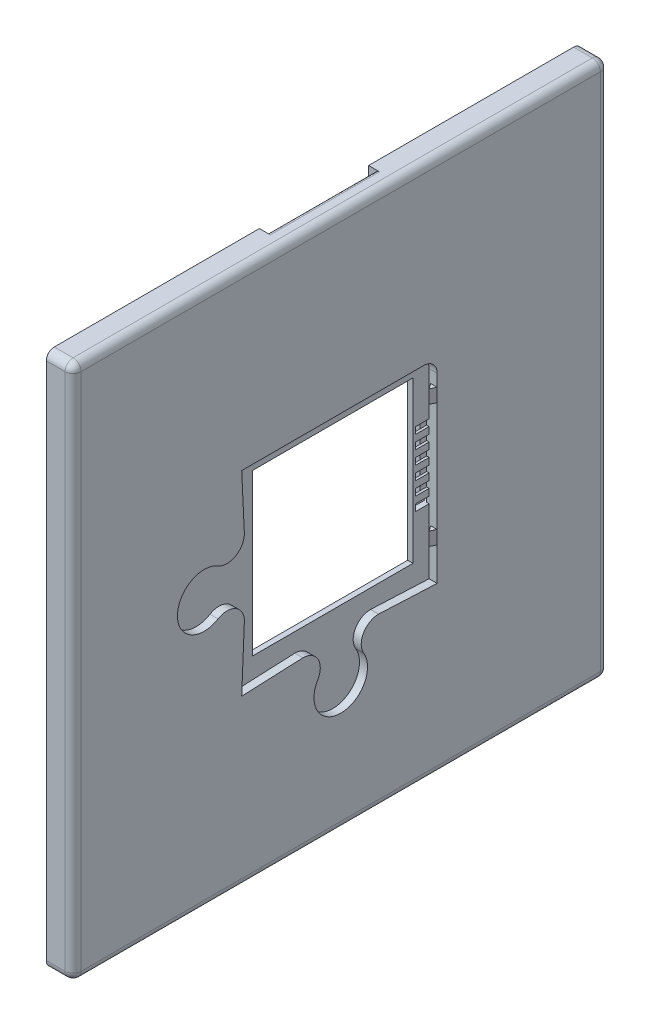
SolidWorks part; units mm, degrees
ref_plane "Front Plane" through (0, 0, 0) normal (0, 0, 1) x (1, 0, 0)
ref_plane "Top Plane" through (0, 0, 0) normal (0, 1, 0) x (1, 0, 0)
ref_plane "Right Plane" through (0, 0, 0) normal (1, 0, 0) x (0, 0, -1)
sketch "Sketch1" plane through (0, 0, 0) normal (1, 0, 0) x (0, 0, -1)
  line L1 (-100, 100) -> (100, 100)
  line L2 (-100, 100) -> (-100, -100)
  line L3 (-100, -100) -> (100, -100)
  line L4 (100, 100) -> (100, -100)
  point P6 (-100, 0)
  dimension "D1" = 200
  dimension "D2" = 200
  dimension "D3" = 100
extrude "Boss-Extrude1" add sketch "Sketch1" along normal blind 10
sketch "Sketch2" plane through (0, 0, 0) normal (-1, 0, 0) x (0, 0, 1)
  line L0 (-35.5, 35.5) -> (-25.5, 35.5)
  line L1 (-35.5, 35.5) -> (-25.5, 35.5)
  line L2 (-35.5, 35.5) -> (-35.5, -35.5)
  line L3 (-35.5, -35.5) -> (35.5, -35.5)
  line L4 (35.5, 35.5) -> (35.5, -35.5)
  line L5 (-25.5, 35.5) -> (-5, 44.5)
  line L6 (-5, 44.5) -> (5, 44.5)
  line L7 (5, 44.5) -> (25.5, 35.5)
  line L8 (25.5, 35.5) -> (35.5, 35.5)
  line L9 (25.5, 35.5) -> (35.5, 35.5)
  line L10 (36.5, 35.5) -> (36.5, -36.5)
  line L11 (-36.5, -36.5) -> (36.5, -36.5)
  line L12 (-36.5, 35.5) -> (-36.5, -36.5)
  line L13 (-35.5, 36.5) -> (-25.5, 36.5)
  line L14 (-25.902, 36.4156) -> (-5.2098, 45.5)
  line L15 (-5.2098, 45.5) -> (5.2098, 45.5)
  line L16 (5.2098, 45.5) -> (25.902, 36.4156)
  line L17 (25.5, 36.5) -> (35.5, 36.5)
  line L18 (-36.5, 35.5) -> (-36.5, 36.5)
  line L19 (-36.5, 36.5) -> (-35.5, 36.5)
  line L20 (35.5, 36.5) -> (36.5, 36.5)
  line L21 (36.5, 36.5) -> (36.5, 35.5)
  point P5 (0, -35.5)
  point P12 (35.5, 0)
  dimension "D1" = 10
  dimension "D2" = 71
  dimension "D3" = 71
  dimension "D4" = 10
  dimension "D5" = 10
  dimension "D6" = 80
  dimension "D7" = 20.5
  dimension "D8" = 1
extrude "Cut-Extrude1" cut sketch "Sketch2" against normal blind 5 contours L21 L20 L17 L16 L15 L14 L13 L19 L18 L12 L11 L10 L7 L8 L4 L3 L2 L0 L5 L6 | L8 L7 L6 L5 L0 L2 L3 L4 region at (0, 2.0136, 0) region at (0, -0.5, 36.3902)
sketch "Sketch3" plane through (5, 0, 0) normal (-1, 0, 0) x (0, 0, 1)
  line L1 (-30, 30) -> (30, 30)
  line L2 (-30, 30) -> (-30, -30)
  line L3 (-30, -30) -> (30, -30)
  line L4 (30, 30) -> (30, -30)
  point P4 (0, -30)
  point P6 (30, 0)
  dimension "D1" = 60
  dimension "D2" = 60
extrude "Cut-Extrude2" cut sketch "Sketch3" against normal through all
sketch "Sketch4" plane through (10, 0, 0) normal (1, 0, 0) x (0, 0, -1)
  line L2 (-36, 35) -> (-36, 14.1421) construction
  line L3 (-36, -37) -> (-14.1421, -37) construction
  line L8 (36, 30) -> (36, -37)
  line L9 (37, -38) -> (-37, -38) construction
  line L10 (-37, 37) -> (37, 37) construction
  line L11 (-37, 37) -> (-37, -38) construction
  line L13 (37, 37) -> (37, -38) construction
  line L14 (14.1421, -37) -> (36, -37) construction
  line L15 (31, 35) -> (-36, 35)
  line L16 (-36, -14.1421) -> (-36, -37) construction
  line L17 (-36, 14.1421) -> (-37, 35)
  line L18 (-37, 35) -> (-36, 35)
  line L19 (-14.1421, -37) -> (-37, -38)
  line L20 (-37, -38) -> (-36, -14.1421)
  line L21 (14.1421, -37) -> (36, -38)
  line L22 (36, -38) -> (36, -37)
  arc A6 (-8.571, -46.8485) -> (8.571, -46.8485) centre (0, -52) ccw
  arc A7 (14.1421, -37) -> (8.571, -46.8485) centre (14.1421, -43.5) ccw
  arc A8 (-8.571, -46.8485) -> (-14.1421, -37) centre (-14.1421, -43.5) ccw
  arc A9 (-45.8485, 8.571) -> (-36, 14.1421) centre (-42.5, 14.1421) ccw
  arc A10 (-36, -14.1421) -> (-45.8485, -8.571) centre (-42.5, -14.1421) ccw
  arc A11 (-45.8485, 8.571) -> (-45.8485, -8.571) centre (-51, 0) ccw
  arc A12 (31, 35) -> (36, 30) centre (31, 30) cw
  point P9 (36, 35)
  point P22 (0.5, -0.5)
  point P24 (0, 0)
  dimension "D3" = 2
  dimension "D4" = 2
  dimension "D6" = 15
  dimension "D8" = 1
  dimension "D9" = 1
  dimension "D12" = 20
  dimension "D13" = 13
  dimension "D14" = 13
  dimension "D7" = 20.8579
  dimension "D5" = 5
  dimension "D1" = 72
  dimension "D2" = 72
  dimension "D10" = 1
  dimension "D11" = 15
  dimension "D15" = 36
extrude "Cut-Extrude3" cut sketch "Sketch4" against normal blind 3
sketch "Sketch8" plane through (0, 0, 0) normal (-1, 0, 0) x (0, 0, 1)
  line L1 (20.4, 100) -> (-20.4, 100)
  line L2 (20.4, 100) -> (20.4, 90.8)
  line L3 (20.4, 90.8) -> (-20.4, 90.8)
  line L4 (-20.4, 100) -> (-20.4, 90.8)
  line L5 (-100, -100) -> (-100, 100) construction
  line L6 (-100, 100) -> (100, 100) construction
  dimension "D2" = 79.6
  dimension "D3" = 40.8
  dimension "D4" = 9.2
extrude "Cut-Extrude4" cut sketch "Sketch8" against normal blind 2.6
shell "Shell1" [suppressed] thickness 5
sketch "Sketch9" plane through (0, 0, 0) normal (-1, 0, 0) x (0, 0, 1)
  line L0 (-95, 95) -> (-95, -95)
  line L1 (-95, -95) -> (95, -95)
  line L2 (95, -95) -> (95, 95)
  line L3 (95, 95) -> (25.4, 95)
  line L4 (25.4, 95) -> (25.4, 85.8)
  line L5 (25.4, 85.8) -> (-25.4, 85.8)
  line L6 (-25.4, 85.8) -> (-25.4, 95)
  line L7 (-25.4, 95) -> (-95, 95)
  line L8 (-41.5, 41.5) -> (-41.5, -41.5)
  line L9 (-41.5, -41.5) -> (41.5, -41.5)
  line L10 (41.5, -41.5) -> (41.5, 41.5)
  line L14 (-100, -100) -> (-100, 100) construction
  line L15 (-100, 100) -> (-20.4, 100) construction
  line L16 (-20.4, 100) -> (-20.4, 90.8) construction
  line L17 (20.4, 90.8) -> (20.4, 100) construction
  line L18 (-20.4, 90.8) -> (20.4, 90.8) construction
  line L19 (100, 100) -> (100, -100) construction
  line L20 (100, -100) -> (-100, -100) construction
  line L21 (-36.5, -36.5) -> (-36.5, 36.5) construction
  line L22 (-36.5, -36.5) -> (36.5, -36.5) construction
  line L23 (36.5, 36.5) -> (36.5, -36.5) construction
  line L24 (-5.2098, 45.5) -> (5.2098, 45.5)
  line L27 (-41.5, 41.5) -> (-19.2962, 41.5)
  line L28 (-19.2962, 41.5) -> (-5.6295, 47.5)
  line L29 (-5.6295, 47.5) -> (5.6295, 47.5) construction
  line L30 (5.6295, 47.5) -> (19.2962, 41.5)
  line L32 (19.2962, 41.5) -> (41.5, 41.5)
  line L33 (-36.5, 36.5) -> (-25.7098, 36.5) construction
  line L35 (-25.7098, 36.5) -> (-5.2098, 45.5) construction
  line L36 (5.2098, 45.5) -> (25.7098, 36.5) construction
  line L37 (-5.2098, 45.5) -> (5.2098, 45.5) construction
  line L38 (5.2098, 45.5) -> (25.7098, 36.5) construction
  line L39 (25.7098, 36.5) -> (36.5, 36.5) construction
  line L40 (-25.7098, 36.5) -> (-5.2098, 45.5) construction
  line L41 (-12.5, -41.5) -> (-12.5, -64.5)
  line L42 (-12.5, -64.5) -> (12.5, -64.5)
  line L43 (12.5, -64.5) -> (12.5, -41.5)
  line L44 (41.5, 12.5) -> (64.5, 12.5)
  line L45 (64.5, 12.5) -> (64.5, -12.5)
  line L46 (64.5, -12.5) -> (41.5, -12.5)
  line L47 (-5.2098, 45.5) -> (-5.6295, 47.5)
  line L48 (5.2098, 45.5) -> (5.6295, 47.5)
  point P59 (64.5, 0)
  point P62 (41.5, 0)
  point P63 (0, -64.5)
  point P64 (0, -41.5)
  line M34 (-5.2098, 45.5) -> (5.2098, 45.5)
  dimension "D1" = 5
  dimension "D2" = 5
  dimension "D3" = 5
  dimension "D4" = 5
  dimension "D5" = 5
  dimension "D6" = 5
  dimension "D7" = 5
  dimension "D8" = 5
  dimension "D9" = 5
  dimension "D10" = 5
  dimension "D11" = 5
  dimension "D12" = 5
  dimension "D13" = 2
  dimension "D14" = 2
  dimension "D15" = 5
  dimension "D16" = 2
  dimension "D17" = 25
  dimension "D18" = 25
  dimension "D19" = 23
  dimension "D20" = 23
extrude "Cut-Extrude5" cut sketch "Sketch9" against normal blind 7 contours L6 L7 L0 L1 L2 L3 L4 L5 L45 L46 L10 L9 L43 L42 L41 L8 L27 L28 L29 L30 L32 L44 | L29 L47 L48 M34 region at (0, 92.313, -60.2) region at (0, 46.5129, 0)
fillet "Fillet1" radius 3 3 edges at (5, 100, 100) (10, 100, 0) (10, 0, 100)
sketch "Sketch10" plane through (0, -64.5, 0) normal (0, -1, 0) x (1, 0, 0)
  line L0 (7, -12.5) -> (7, 12.5) construction
  line L1 (2.9, -2.6) -> (6, -2.6)
  line L2 (2.9, -2.6) -> (2.9, 2.6)
  line L3 (2.9, 2.6) -> (6, 2.6)
  line L4 (6, -2.6) -> (6, 2.6)
  line L6 (7, -12.5) -> (0, -12.5) construction
  point P8 (2.9, 0)
  dimension "D1" = 5.2
  dimension "D2" = 3.1
  dimension "D3" = 1
  dimension "D4" = 12.5
extrude "Cut-Extrude6" cut sketch "Sketch10" against normal blind 12.5
fillet "Fillet2" radius 1 4 edges at (4.45, -64.5, -2.6) (6, -64.5, 0) (4.45, -64.5, 2.6) (2.9, -64.5, 0)
sketch "Sketch11" plane through (0, 0, 64.5) normal (0, 0, 1) x (1, 0, 0)
  line L1 (2.9, 2.6) -> (6, 2.6)
  line L2 (2.9, 2.6) -> (2.9, -2.6)
  line L3 (2.9, -2.6) -> (6, -2.6)
  line L4 (6, 2.6) -> (6, -2.6)
  line L5 (7, -12.5) -> (0, -12.5) construction
  line L6 (7, 12.5) -> (7, -12.5) construction
  point P4 (2.9, 0)
  dimension "D1" = 3.1
  dimension "D2" = 5.2
  dimension "D3" = 12.5
  dimension "D4" = 1
extrude "Cut-Extrude7" cut sketch "Sketch11" against normal blind 13.5
fillet "Fillet3" radius 1 4 edges at (2.9, 0, 64.5) (4.45, -2.6, 64.5) (6, 0, 64.5) (4.45, 2.6, 64.5)
fillet "Fillet4" radius 4 4 edges at (3.5, 12.5, 64.5) (3.5, -12.5, 64.5) (3.5, -64.5, 12.5) (3.5, -64.5, -12.5)
sketch "Sketch12" plane through (0, 0, 0) normal (-1, 0, 0) x (0, 0, 1)
  line L0 (-95, 95) -> (-95, -95) construction
  line L1 (-95, -84.8) -> (-99, -84.8)
  line L2 (-95, -84.8) -> (-95, -90)
  line L3 (-95, -90) -> (-99, -90)
  line L4 (-99, -84.8) -> (-99, -90)
  line L5 (-100, -100) -> (-100, 100) construction
  line L6 (100, -100) -> (-100, -100) construction
  dimension "D1" = 1
  dimension "D2" = 10
  dimension "D3" = 5.2
extrude "Cut-Extrude8" cut sketch "Sketch12" against normal blind 2
sketch "Sketch13" plane through (2, 0, 0) normal (-1, 0, 0) x (0, 0, 1)
  line L0 (-99, -90) -> (-95, -90) construction
  line L1 (-99, -84.8) -> (-96, -84.8)
  line L2 (-99, -84.8) -> (-99, -90)
  line L3 (-99, -90) -> (-96, -90)
  line L4 (-96, -84.8) -> (-96, -90)
  dimension "D1" = 3
extrude "Cut-Extrude9" cut sketch "Sketch13" against normal blind 6
sketch "Sketch14" plane through (7, 0, 0) normal (-1, 0, 0) x (0, 0, 1)
  line L0 (95, -95) -> (95, 95) construction
  line L1 (95, -82.4) -> (92, -82.4)
  line L2 (95, -82.4) -> (95, -92.4)
  line L3 (95, -92.4) -> (92, -92.4)
  line L4 (92, -82.4) -> (92, -92.4)
  line L5 (-99, -84.8) -> (-99, -90) construction
  point P8 (-99, -87.4)
  point P9 (92, -87.4)
  dimension "D1" = 10
  dimension "D2" = 3
extrude "Boss-Extrude2" add sketch "Sketch14" along normal blind 7
sketch "Sketch16" plane through (0, 0, 92) normal (0, 0, -1) x (-1, 0, 0)
  line L0 (0, -82.4) -> (0, -92.4) construction
  line L1 (-4.2, -84.9) -> (-1, -84.9)
  line L2 (-4.2, -84.9) -> (-4.2, -89.9)
  line L3 (-4.2, -89.9) -> (-1, -89.9)
  line L4 (-1, -84.9) -> (-1, -89.9)
  point P6 (0, -87.4)
  point P7 (-1, -87.4)
  dimension "D1" = 3.2
  dimension "D2" = 1
  dimension "D3" = 5
extrude "Cut-Extrude10" cut sketch "Sketch16" against normal blind 6
fillet "Fillet5" radius 1 3 edges at (2.6, -89.9, 92) (4.2, -87.4, 92) (2.6, -84.9, 92)
sketch "Sketch17" plane through (0, 0, 0) normal (-1, 0, 0) x (0, 0, 1)
  line L1 (-65.5796, 65.977) -> (65.5796, 65.977)
  line L2 (-65.5796, 65.977) -> (-65.5796, -65.977)
  line L3 (-65.5796, -65.977) -> (65.5796, -65.977)
  line L4 (65.5796, 65.977) -> (65.5796, -65.977)
  point P4 (0, 65.977)
  point P6 (-65.5796, 0)
  dimension "D1" = 131.954
  dimension "D2" = 131.1591
extrude "Cut-Extrude11" cut sketch "Sketch17" against normal blind 2.1
sketch "Sketch18" plane through (0, 0, 0) normal (-1, 0, 0) x (0, 0, 1)
  line L0 (100, -100) -> (-100, -100) construction
  line L1 (-100, -100) -> (-100, 100) construction
  line L2 (20.4, 100) -> (-20.4, 100) construction
  line L3 (-20.4, 100) -> (-20.4, 90.8) construction
  line L4 (-20.4, 90.8) -> (20.4, 90.8) construction
  line L5 (20.4, 90.8) -> (20.4, 100) construction
  line L6 (20.4, 100) -> (97, 100) construction
  line L7 (100, 97) -> (100, -100) construction
  line L8 (100, -100) -> (-100, -100) construction
  line L9 (-100, -100) -> (-100, 100) construction
  line L10 (-100, 100) -> (-20.4, 100) construction
  line L11 (-20.4, 100) -> (-20.4, 90.8) construction
  line L12 (-20.4, 90.8) -> (20.4, 90.8) construction
  line L13 (20.4, 90.8) -> (20.4, 100) construction
  line L14 (20.4, 100) -> (97, 100) construction
  line L15 (100, 97) -> (100, -100) construction
  line L16 (-97, 97) -> (-23.4, 97)
  line L17 (-23.4, 97) -> (-23.4, 88.4)
  line L18 (-23.4, 88.4) -> (23.4, 88.4)
  line L19 (23.4, 88.4) -> (23.4, 97)
  line L20 (23.4, 97) -> (97, 97)
  line L21 (97, 97) -> (97, -97)
  line L22 (97, -97) -> (-97, -97)
  line L23 (-97, -97) -> (-97, 97)
  line L24 (92, -92.4) -> (97, -92.4)
  line L25 (97, -92.4) -> (97, -82.4)
  line L26 (97, -82.4) -> (92, -82.4)
  line L27 (92, -82.4) -> (92, -92.4)
  line L28 (95, -82.4) -> (92, -82.4) construction
  arc A1 (100, 97) -> (97, 100) centre (97, 97) ccw construction
  arc A3 (100, 97) -> (97, 100) centre (97, 97) ccw construction
  point P19 (23.4, 92.7)
  line M19 (-95, -95) -> (-95, -90)
  line M20 (-95, -90) -> (-99, -90)
  line M22 (-99, -84.8) -> (-95, -84.8)
  line M23 (-95, -84.8) -> (-95, 95)
  line M24 (-95, 95) -> (-25.4, 95)
  line M25 (-25.4, 95) -> (-25.4, 85.8)
  line M26 (-25.4, 85.8) -> (25.4, 85.8)
  line M27 (25.4, 85.8) -> (25.4, 95)
  line M28 (25.4, 95) -> (95, 95)
  line M29 (95, 95) -> (95, -82.4)
  line M30 (95, -82.4) -> (92, -82.4)
  line M31 (92, -82.4) -> (92, -92.4)
  line M32 (92, -92.4) -> (95, -92.4)
  line M33 (95, -92.4) -> (95, -95)
  line M34 (95, -95) -> (-95, -95)
  dimension "D2" = 3
  dimension "D1" = 3
  dimension "D3" = 6
  dimension "D4" = 8.6
  dimension "D5" = 3
  dimension "D6" = 3
  dimension "D7" = 46.8
  dimension "D8" = 11.6
  dimension "D9" = 76.6
extrude "Cut-Extrude12" cut sketch "Sketch18" against normal blind 2 contours L26 L21 L20 L19 L18 L17 L16 L23 M22 M23 M24 M25 M26 M27 M28 M29 | L23 M20 M19 M34 M33 M32 M31 M30 M29 M28 M27 M26 M25 M24 M23 M22 | L24 L23 L22 L21 M33 M34 M19 M20 region at (0, 96.7341, -60.2) region at (0, -1.1382, -0.1068) region at (0, -95.8835, -1.1429)
sketch "Sketch19" plane through (7, 0, 0) normal (1, 0, 0) x (0, 0, -1)
  line L0 (36, -38) -> (36, 30) construction
  line L1 (36, 13.75) -> (31, 13.75)
  line L2 (36, 13.75) -> (36, -13.75)
  line L3 (36, -13.75) -> (31, -13.75)
  line L4 (31, 13.75) -> (31, -13.75)
  line L6 (36, 13.75) -> (31, 13.75)
  line L7 (36, 13.75) -> (36, 11.25)
  line L8 (36, 11.25) -> (31, 11.25)
  line L9 (31, 13.75) -> (31, 11.25)
  line L10 (36, 8.75) -> (31, 8.75)
  line L11 (36, 8.75) -> (36, 6.25)
  line L12 (36, 6.25) -> (31, 6.25)
  line L13 (31, 8.75) -> (31, 6.25)
  line L14 (36, 3.75) -> (31, 3.75)
  line L15 (36, 3.75) -> (36, 1.25)
  line L16 (36, 1.25) -> (31, 1.25)
  line L17 (31, 3.75) -> (31, 1.25)
  line L18 (36, -1.25) -> (31, -1.25)
  line L19 (36, -1.25) -> (36, -3.75)
  line L20 (36, -3.75) -> (31, -3.75)
  line L21 (31, -1.25) -> (31, -3.75)
  line L22 (36, -6.25) -> (31, -6.25)
  line L23 (36, -6.25) -> (36, -8.75)
  line L24 (36, -8.75) -> (31, -8.75)
  line L25 (31, -6.25) -> (31, -8.75)
  line L26 (36, -11.25) -> (31, -11.25)
  line L27 (36, -11.25) -> (36, -13.75)
  line L28 (36, -13.75) -> (31, -13.75)
  line L29 (31, -11.25) -> (31, -13.75)
  line L30 (30, -30) -> (30, 30) construction
  point P25 (31, 0)
  line M32 (36, -38) -> (36, 30)
  dimension "D2" = 2.5
  dimension "D3" = 2.5
  dimension "D4" = 2.5
  dimension "D5" = 2.5
  dimension "D6" = 2.5
  dimension "D7" = 2.5
  dimension "D8" = 2.5
  dimension "D9" = 2.5
  dimension "D10" = 2.5
  dimension "D11" = 2.5
  dimension "D12" = 2.5
  dimension "D13" = 1
extrude "Cut-Extrude13" cut sketch "Sketch19" against normal through all contours L26 L4 L3 M32 | L24 L2 L22 L4 | L20 L2 L18 L4 | L16 L2 L14 L4 | L12 L2 L10 L4 | L8 L2 L1 L4 region at (7, 12.5, -33.5) region at (7, 7.5, -33.5) region at (7, 2.5, -33.5) region at (7, -2.5, -33.5) region at (7, -7.5, -33.5) region at (7, -12.5, -33.5)
sketch "Sketch20" plane through (2.1, 0, 0) normal (-1, 0, 0) x (0, 0, 1)
  line L0 (-41.5, 41.5) -> (-41.5, -41.5) construction
  line L1 (-31, 13.75) -> (-41.5, 13.75)
  line L2 (-31, 13.75) -> (-31, -13.75)
  line L3 (-31, -13.75) -> (-41.5, -13.75)
  line L4 (-41.5, 13.75) -> (-41.5, -13.75)
  line L5 (-31, -13.75) -> (-36, -13.75) construction
  line L6 (-31, -13.75) -> (-31, -11.25) construction
extrude "Cut-Extrude14" cut sketch "Sketch20" against normal blind 4
chamfer "Chamfer1" distance 0.9 angle 45 1 edges at (5, 0, -31)
sketch "Sketch33" plane through (2.1, 0, 0) normal (-1, 0, 0) x (0, 0, 1)
  line L0 (-41.5, 13.75) -> (-41.5, 41.5) construction
  line L1 (-41.5, 18.75) -> (-36.5, 18.75)
  line L2 (-41.5, 18.75) -> (-41.5, -18.75)
  line L3 (-41.5, -18.75) -> (-36.5, -18.75)
  line L4 (-36.5, 18.75) -> (-36.5, -18.75)
  line L5 (-36.5, -13.75) -> (-36.5, -36.5) construction
  line L6 (-36.5, 13.75) -> (-41.5, 13.75) construction
  line L7 (-41.5, -13.75) -> (-36, -13.75) construction
  dimension "D1" = 5
  dimension "D2" = 5
extrude "Boss-Extrude10" add sketch "Sketch33" along normal blind 1 and the other way blind 1
sketch "Sketch34" plane through (0, 0, -41.5) normal (0, 0, -1) x (-1, 0, 0)
  line L0 (-3.1, 13.75) -> (-3.1, 17) construction
  line L1 (-6.1, 17) -> (-3.1, 17)
  line L2 (-6.1, 17) -> (-6.1, -17)
  line L3 (-6.1, -17) -> (-3.1, -17)
  line L4 (-3.1, 17) -> (-3.1, -17)
  line L5 (-6.1, 13.75) -> (-3.1, 13.75) construction
  line L6 (-6.1, -13.75) -> (-3.1, -13.75) construction
  line L7 (-3.1, -13.75) -> (-3.1, -17) construction
  line L8 (-7, 13.75) -> (-7, 30) construction
  dimension "D1" = 3
  dimension "D2" = 34
  dimension "D3" = 0.9
extrude "Cut-Extrude19" cut sketch "Sketch34" against normal blind 3
chamfer "Chamfer2" distance 1 angle 45 4 edges at (4.6, -17, -41.5) (3.1, 0, -41.5) (4.6, 17, -41.5) (6.1, 0, -41.5)
sketch "Sketch24" plane through (7, 0, 0) normal (-1, 0, 0) x (0, 0, 1)
  line L0 (-95, 95) -> (95, -95) construction
  line L1 (-95, -95) -> (95, 95) construction
  circle A0 centre (80, -80) radius 5
  circle A1 centre (80, -80) radius 0.75
  circle A2 centre (-80, -80) radius 0.75
  circle A3 centre (-80, -80) radius 5
  dimension "D1" = 10
  dimension "D2" = 1.5
  dimension "D4" = 1.5
  dimension "D5" = 10
  dimension "D3" = 15
  dimension "D6" = 15
extrude "Boss-Extrude5" add sketch "Sketch24" along normal blind 5
mirror "Mirror1" about plane through (0, 0, 0) normal (0, 1, 0) of "Boss-Extrude5"
sketch "Sketch25" plane through (2.1, 0, 0) normal (-1, 0, 0) x (0, 0, 1)
  line L0 (36.5, 36.5) -> (41.5, 41.5) construction
  line L1 (41.5, -41.5) -> (36.5, -36.5) construction
  line L2 (-41.5, -41.5) -> (-36.5, -36.5) construction
  line L3 (-41.5, 41.5) -> (-36.5, 36.5) construction
  line L5 (12.5, -41.5) -> (41.5, -41.5) construction
  line L6 (19.2962, 41.5) -> (41.5, 41.5) construction
  line L7 (-19.2962, 41.5) -> (-41.5, 41.5) construction
  circle A0 centre (-38.5, 38.5) radius 0.75
  circle A1 centre (38.5, 38.5) radius 0.75
  circle A2 centre (38.5, -38.5) radius 0.75
  circle A3 centre (-38.5, -38.5) radius 0.75
  dimension "D1" = 1.5
  dimension "D2" = 1.5
  dimension "D3" = 1.5
  dimension "D4" = 1.5
  dimension "D5" = 3
  dimension "D6" = 3
  dimension "D7" = 3
  dimension "D8" = 3
extrude "Cut-Extrude16" cut sketch "Sketch25" against normal blind 3.5
sketch "Sketch27" plane through (0, 95, 0) normal (0, -1, 0) x (1, 0, 0)
  line L0 (7, -25.4) -> (7, -95) construction
  line L1 (7, -41.5) -> (2, -41.5)
  line L2 (7, -41.5) -> (7, -65.5)
  line L3 (7, -65.5) -> (2, -65.5)
  line L4 (2, -41.5) -> (2, -65.5)
  line L5 (2, -95) -> (2, -25.4) construction
  line L6 (2, -97) -> (2, -23.4) construction
  line L8 (7, -45.5) -> (4.5, -45.5)
  line L9 (7, -45.5) -> (7, -61.5)
  line L10 (7, -61.5) -> (4.5, -61.5)
  line L11 (4.5, -45.5) -> (4.5, -61.5)
  line M5 (2, -25.4) -> (2, -95)
  line M7 (7, -95) -> (7, -25.4)
  dimension "D1" = 24
  dimension "D2" = 2.5
  dimension "D3" = 4
  dimension "D4" = 4
extrude "Boss-Extrude6" add sketch "Sketch27" along normal blind 8 contours L11 L8 L2 L1 L3 L10 M5 M7 region at (3.875, 95, -53.5)
sketch "Sketch28" plane through (2, 0, 0) normal (-1, 0, 0) x (0, 0, 1)
  line L0 (-65.5, 87) -> (-65.5, 95) construction
  line L1 (-61.5, 95) -> (-45.5, 95)
  line L2 (-61.5, 95) -> (-61.5, 90)
  line L3 (-61.5, 90) -> (-45.5, 90)
  line L4 (-45.5, 95) -> (-45.5, 90)
  line L5 (-41.5, 87) -> (-41.5, 95) construction
  line L6 (-95, 95) -> (-65.5, 95) construction
  dimension "D1" = 4
  dimension "D2" = 4
  dimension "D3" = 5
extrude "Cut-Extrude17" cut sketch "Sketch28" against normal up to next
sketch "Sketch30" plane through (7, 0, 0) normal (-1, 0, 0) x (0, 0, 1)
  line L0 (25.4, 95) -> (95, 95) construction
  line L1 (41.5, -41.5) -> (95, -95) construction
  line L3 (-95, -95) -> (95, -95) construction
  line L4 (-41.5, -41.5) -> (-95, -95) construction
  line L5 (-95, 95) -> (-41.5, 41.5) construction
  line L7 (-82, -84.5826) -> (-78, -84.5826)
  line L10 (95, -82.4) -> (95, 95) construction
  line L11 (84.5826, 82) -> (95, 82)
  line L12 (84.5826, 82) -> (84.5826, 78)
  line L13 (84.5826, 78) -> (95, 78)
  line L14 (95, 82) -> (95, 78)
  line L15 (95, 95) -> (25.4, 95) construction
  line L16 (78, 84.5826) -> (82, 84.5826)
  line L17 (78, 84.5826) -> (78, 95)
  line L18 (78, 95) -> (82, 95)
  line L19 (82, 84.5826) -> (82, 95)
  line L20 (-95, -95) -> (-95, 95) construction
  line L21 (-75.4174, 78) -> (-95, 78)
  line L22 (-75.4174, 78) -> (-75.4174, 82)
  line L23 (-75.4174, 82) -> (-95, 82)
  line L24 (-95, 78) -> (-95, 82)
  line L25 (95, -95) -> (-95, -95) construction
  line L26 (-82, 75.4174) -> (-78, 75.4174)
  line L27 (-82, 75.4174) -> (-82, -75.4174)
  line L28 (-82, -75.4174) -> (-78, -75.4174)
  line L29 (-78, 75.4174) -> (-78, -75.4174)
  line L30 (82, 75.4174) -> (78, 75.4174)
  line L31 (82, 75.4174) -> (82, -75.4174)
  line L32 (82, -75.4174) -> (78, -75.4174)
  line L33 (78, 75.4174) -> (78, -75.4174)
  line L34 (-75.4174, -78) -> (75.4174, -78)
  line L35 (-75.4174, -78) -> (-75.4174, -82)
  line L36 (-75.4174, -82) -> (75.4174, -82)
  line L37 (75.4174, -78) -> (75.4174, -82)
  line L38 (-41.5, -41.5) -> (-37.5, -41.5)
  line L39 (-41.5, -41.5) -> (-41.5, -95)
  line L40 (-41.5, -95) -> (-37.5, -95)
  line L41 (-37.5, -41.5) -> (-37.5, -95)
  line L42 (-95, 95) -> (-95, -95) construction
  line L43 (-41.5, -41.5) -> (-95, -41.5)
  line L44 (-41.5, -41.5) -> (-41.5, -37.5)
  line L45 (-41.5, -37.5) -> (-95, -37.5)
  line L46 (-95, -41.5) -> (-95, -37.5)
  line L47 (97, -97) -> (-97, -97) construction
  line L48 (41.5, -41.5) -> (37.5, -41.5)
  line L49 (41.5, -41.5) -> (41.5, -97)
  line L50 (41.5, -97) -> (37.5, -97)
  line L51 (37.5, -41.5) -> (37.5, -97)
  line L52 (-41.5, 41.5) -> (-19.2962, 41.5) construction
  line L53 (41.5, -41.5) -> (95, -41.5)
  line L54 (41.5, -41.5) -> (41.5, -37.5)
  line L55 (41.5, -37.5) -> (95, -37.5)
  line L56 (95, -41.5) -> (95, -37.5)
  line L57 (-82, 41.5) -> (-95, 41.5)
  line L58 (-82, 41.5) -> (-82, 37.5)
  line L59 (-82, 37.5) -> (-95, 37.5)
  line L60 (-95, 41.5) -> (-95, 37.5)
  line L61 (41.5, 41.5) -> (95, 41.5)
  line L62 (41.5, 41.5) -> (41.5, 37.5)
  line L63 (41.5, 37.5) -> (95, 37.5)
  line L64 (95, 41.5) -> (95, 37.5)
  line L65 (41.5, 41.5) -> (37.5, 41.5)
  line L66 (41.5, 41.5) -> (41.5, 95)
  line L67 (41.5, 95) -> (37.5, 95)
  line L68 (37.5, 41.5) -> (37.5, 95)
  line L69 (-82, -84.5826) -> (-82, -95)
  line L70 (41.5, 82) -> (75.4174, 82)
  line L71 (41.5, 82) -> (41.5, 78)
  line L72 (41.5, 78) -> (75.4174, 78)
  line L73 (75.4174, 82) -> (75.4174, 78)
  line L74 (-82, -95) -> (-78, -95)
  line L75 (-78, -84.5826) -> (-78, -95)
  line L76 (-65.5, 95) -> (-95, 95) construction
  line L77 (-75.4174, -78) -> (-95, -78)
  line L78 (-75.4174, -78) -> (-75.4174, -82)
  line L79 (-75.4174, -82) -> (-95, -82)
  line L80 (-95, -78) -> (-95, -82)
  line L81 (-82, 95) -> (-78, 95)
  line L82 (-82, 95) -> (-82, 84.5826)
  line L83 (-82, 84.5826) -> (-78, 84.5826)
  line L84 (-78, 95) -> (-78, 84.5826)
  line L86 (84.5826, -78) -> (95, -78)
  line L87 (84.5826, -78) -> (84.5826, -82)
  line L88 (84.5826, -82) -> (95, -82)
  line L89 (95, -78) -> (95, -82)
  circle A0 centre (80, 80) radius 5 construction
  circle A1 centre (80, 80) radius 5 construction
  circle A2 centre (-80, 80) radius 5 construction
  circle A3 centre (-80, 80) radius 5 construction
  circle A4 centre (-80, 80) radius 5 construction
  circle A5 centre (-80, -80) radius 5 construction
  circle A6 centre (80, -80) radius 5 construction
  circle A7 centre (-80, -80) radius 5 construction
  circle A8 centre (80, -80) radius 5 construction
  circle A9 centre (-80, 80) radius 5 construction
  dimension "D2" = 4
  dimension "D3" = 4
  dimension "D4" = 4
  dimension "D5" = 4
  dimension "D6" = 4
  dimension "D7" = 4
  dimension "D8" = 4
  dimension "D9" = 4
  dimension "D10" = 4
  dimension "D11" = 4
  dimension "D12" = 4
  dimension "D13" = 4
  dimension "D14" = 4
  dimension "D15" = 4
  dimension "D16" = 4
  dimension "D17" = 4
  dimension "D18" = 4
  dimension "D19" = 4
extrude "Boss-Extrude8" add sketch "Sketch30" along normal blind 2.5 contours L34 L49 L36 | L55 L53 L33 | L55 L33 L53 L31 | L53 L33 L31 | L55 L31 L53 | L63 L33 L55 L31 | L51 L34 L49 | L36 L51 L49 | L51 L34 L41 L36 | L41 L36 L39 | L39 L34 L36 | L41 L39 L34 | L41 L34 L39 L36 | L34 L51 L36 L49 | L45 L29 L43 | L29 L45 L27 L43 | L27 L45 L43 | L45 L29 L27 | L23 L21 | L59 L27 L57 | L29 L43 L27 | L68 L66 | L63 L33 L61 | L33 L63 L31 L61 | L31 L63 L61 | L33 L61 L31 | L66 L72 L70 | L13 L11 | L19 L17 | L79 L77 | L75 L69 | L88 L86 | L84 L82 | L53 L56 L55 L54 | L29 L28 L27 L26 | L59 L60 L57 L58 | L66 L67 L68 L65 region at (7, -89.7913, -80) region at (7, 80, 89.7913) region at (7, 89.7913, 80) region at (7, 80, -85.2087) region at (7, 68.25, 39.5) region at (7, -39.5, 59.75) region at (7, -59.75, -39.5) region at (7, 18.9587, -80) region at (7, 39.5, -88.5) region at (7, -39.5, -59.75) region at (7, -39.5, -80) region at (7, -58.4587, -80) region at (7, -39.5, -88.5) region at (7, -80, -58.4587) region at (7, -80, -39.5) region at (7, -80, 0) region at (7, -80, -85.2087) region at (7, -88.5, -39.5) region at (7, -59.75, 39.5) region at (7, -80, 39.5) region at (7, -80, 58.4587) region at (7, -89.5, 39.5) region at (7, -58.4587, 80) region at (7, -39.5, 80) region at (7, 0, 80) region at (7, -39.5, 88.5) region at (7, 39.5, 59.75) region at (7, 39.5, 80) region at (7, 58.4587, 80) region at (7, 39.5, 88.5) region at (7, 80, 58.4587) region at (7, 89.7913, -80) region at (7, -80, 89.7913)
fillet "Fillet10" radius 3 89 edges at (5.75, 37.5, 95) (4.5, -82.4, 95) (4.5, -95, -95) (5.75, -41.5, -78) (5.75, -37.5, -78) (5.75, -41.5, -37.5) (5.75, -82, 37.5) (5.75, -41.5, 37.5) (5.75, -78, 37.5) (5.75, -95, 37.5) (5.75, -95, 41.5) (5.75, -82, 41.5) (5.75, -78, 41.5) (5.75, -37.5, 41.5) (5.75, -41.5, 41.5) (5.75, -37.5, 95) (5.75, -41.5, 95) (5.75, -78, 75.4174) (5.75, -82, 75.4174) (5.75, -75.4174, 82) (5.75, -75.4174, 78) (5.75, -41.5, 82) (5.75, -41.5, 78) (5.75, -37.5, 82) (5.75, -37.5, 78) (4.55, -12.5, 41.5) (4.55, 12.5, 41.5) (5.75, 37.5, 41.5) (5.75, 41.5, 41.5) (5.75, 37.5, 78) (5.75, 37.5, 82) (5.75, 41.5, 78) (5.75, 41.5, 82) (5.75, 41.5, 95) (5.75, 78, 41.5) (5.75, 82, 41.5) (5.75, 95, 41.5) (5.75, 82, 95) (4.5, 95, 95) (5.75, 78, 95) (5.75, 82, 84.5826) (5.75, 84.5826, 82) (5.75, 78, 84.5826) (5.75, 95, 82) (5.75, 75.4174, 82) (5.75, 75.4174, 78) (5.75, 78, 75.4174) (5.75, 82, 75.4174) (5.75, 84.5826, 78) (5.75, 95, 78) (5.75, 95, 37.5) (4.5, 95, 25.4) (4.5, 85.8, 25.4) (4.5, 85.8, -25.4) (4.5, 95, -25.4) (4.5, 87, -41.5) (4.5, 95, -41.5) (5.75, 41.5, -95) (5.75, 82, -95) (5.75, -78, -41.5) (5.75, -41.5, -41.5) (5.75, -82, -41.5) (5.75, -95, -41.5) (5.75, -75.4174, -82) (5.75, -75.4174, -78) (5.75, -78, -75.4174) (5.75, -82, -75.4174) (5.75, 37.5, -95) (5.75, 78, -95) (4.5, 95, -95) (5.75, -37.5, -95) (5.75, -37.5, -82) (5.75, -41.5, -95) (5.75, -41.5, -82) (5.75, 37.5, -82) (5.75, 41.5, -82) (5.75, 75.4174, -78) (5.75, 75.4174, -82) (5.75, 78, -84.5826) (5.75, 82, -84.5826) (5.75, -78, -37.5) (5.75, -82, -37.5) (5.75, -84.5826, -78) (5.75, -78, -84.5826) (5.75, -84.5826, -82) (5.75, -82, -84.5826) (4.5, 87, -65.5) (5.75, 95, -78) (5.75, 95, -82)
fillet "Fillet11" radius 3 1 edges at (7, 95, -53.5)
sketch "Sketch32" plane through (2.1, 0, 0) normal (-1, 0, 0) x (0, 0, 1)
  line L0 (5.6295, 47.5) -> (5.2098, 45.5)
  line L1 (5.2098, 45.5) -> (-5.2098, 45.5)
  line L2 (-5.2098, 45.5) -> (-5.6295, 47.5)
  line L3 (-5.6295, 47.5) -> (5.6295, 47.5)
extrude "Boss-Extrude9" add sketch "Sketch32" against normal blind 1.5
fillet "Fillet12" radius 1.5 1 edges at (2.6, 100, 0)
sketch "Sketch35" plane through (5, 0, 0) normal (-1, 0, 0) x (0, 0, 1)
  line L0 (-30, 30) -> (-41.5, 41.5) construction
  line L1 (-36.5, 36.5) -> (-25.7098, 36.5) construction
  circle A0 centre (-32.75, 32.75) radius 2.5
  dimension "D1" = 5
  dimension "D2" = 3.75
extrude "Cut-Extrude20" cut sketch "Sketch35" against normal blind 1.6
sketch "Sketch36" plane through (2.9, 0, 0) normal (1, 0, 0) x (0, 0, -1)
  line L0 (-2.6, -52) -> (2.6, -52) construction
  line L1 (-1.6, -52) -> (1.6, -52)
  line L2 (-1.6, -52) -> (-1.6, -59)
  line L3 (-1.6, -59) -> (1.6, -59)
  line L4 (1.6, -52) -> (1.6, -59)
  line L5 (-2.6, -52) -> (-2.6, -63.5) construction
  line L6 (2.6, -52) -> (2.6, -63.5) construction
  line L7 (-51, 2.6) -> (-51, -2.6) construction
  line L8 (-51, 1.6) -> (-58, 1.6)
  line L9 (-51, 1.6) -> (-51, -1.6)
  line L10 (-51, -1.6) -> (-58, -1.6)
  line L11 (-58, 1.6) -> (-58, -1.6)
  line L12 (-51, 2.6) -> (-63.5, 2.6) construction
  line L13 (-51, -2.6) -> (-63.5, -2.6) construction
  dimension "D1" = 1
  dimension "D2" = 1
  dimension "D3" = 7
  dimension "D4" = 1
  dimension "D5" = 1
  dimension "D6" = 7
extrude "Cut-Extrude21" cut sketch "Sketch36" against normal through all
ref_plane "Plane19" through (6, 0, 0) normal (-1, 0, 0) x (0, 0, 1)
sketch "Sketch43" plane through (0, 35, 0) normal (0, -1, 0) x (1, 0, 0)
  line L0 (7.6, -36) -> (9.0004, -34)
  line L1 (7, -36) -> (10, -36) construction
  line L2 (9.0004, -34) -> (10, -36)
  line L3 (10, -36) -> (10, -31) construction
  line L4 (7.6, -36) -> (10, -36)
  line L5 (7, -36) -> (7, -31) construction
  dimension "D1" = 0.6
  dimension "D2" = 2
  dimension "D3" = 55
extrude "Boss-Extrude12" add sketch "Sketch43" along normal blind 5 from offset 9.55
extrude "Boss-Extrude13" add sketch "Sketch43<2>" along normal blind 5 from offset 55.55
sketch "Sketch43<2>" plane through (0, 35, 0) normal (0, -1, 0) x (1, 0, 0) same geometry as "Sketch43"
fillet "Fillet13" radius 3 7 edges at (3.5, 100, -100) (9.1213, 99.1213, -100) (3.5, -100, 100) (9.1213, -100, 99.1213) (5, -100, -100) (10, -1.5, -100) (10, -100, -1.5)
sketch "Sketch44" plane through (2.6, 0, 0) normal (-1, 0, 0) x (0, 0, 1)
  circle A0 centre (-10, 94) radius 0.75
  circle A1 centre (10, 94) radius 0.75
  dimension "D1" = 1.5
  dimension "D2" = 1.5
extrude "Cut-Extrude22" cut sketch "Sketch44" against normal blind 6
sketch "Sketch45" plane through (2, 0, 0) normal (-1, 0, 0) x (0, 0, 1)
  line L1 (72.9965, -90.0036) -> (61.9965, -90.0036)
  line L2 (72.9965, -90.0036) -> (72.9965, -98.0036)
  line L3 (72.9965, -98.0036) -> (61.9965, -98.0036)
  line L4 (61.9965, -90.0036) -> (61.9965, -98.0036)
  line L5 (69.9965, -98.0036) -> (99.8272, -98.0036) construction
  line L7 (99.8272, -98.0036) -> (-99.8272, -98.0036) construction
  line L8 (9.9965, -90.0036) -> (-10.0035, -90.0036) construction
  line L9 (69.9965, -90.0036) -> (64.9965, -90.0036)
  line L10 (69.9965, -90.0036) -> (69.9965, -98.0036)
  line L11 (69.9965, -98.0036) -> (64.9965, -98.0036)
  line L12 (64.9965, -90.0036) -> (64.9965, -98.0036)
  line L13 (-5.5, -98.0036) -> (5.5, -98.0036)
  line L14 (-5.5, -98.0036) -> (-5.5, -90.0036)
  line L15 (-5.5, -90.0036) -> (5.5, -90.0036)
  line L16 (5.5, -98.0036) -> (5.5, -90.0036)
  line L17 (97, -100) -> (-97, -100) construction
  line L18 (-2.5, -98.0036) -> (2.5, -98.0036)
  line L19 (-2.5, -98.0036) -> (-2.5, -90.0036)
  line L20 (-2.5, -90.0036) -> (2.5, -90.0036)
  line L21 (2.5, -98.0036) -> (2.5, -90.0036)
  line L22 (100, 97) -> (100, -97) construction
  arc A0 (97, -100) -> (100, -97) centre (97, -97) ccw construction
  arc A1 (-100, -97) -> (-97, -100) centre (-97, -97) ccw construction
  point P27 (0, -90.0036)
  line M40 (-97, -97) -> (97, -97)
  line M44 (95, -95) -> (-92, -95)
  dimension "D1" = 3
  dimension "D2" = 3
  dimension "D3" = 5
  dimension "D4" = 3
  dimension "D5" = 3
  dimension "D6" = 1.9964
  dimension "D7" = 5
  dimension "D8" = 27.0035
  dimension "D9" = 8
extrude "Boss-Extrude14" add sketch "Sketch45" against normal up to surface (5 mm away) and the other way up to surface (2 mm away) contours L1 L10 L2 M44 | L1 L12 L10 M44 | L12 L1 L4 M44 | L12 L4 M44 M40 | L12 L4 L3 M40 | L12 L10 M44 M40 | L12 L3 L10 M40 | L10 L3 L2 M40 | L10 L2 M44 M40 | L19 L14 M40 M44 | L19 L15 L14 M44 | L21 L15 L19 M44 | L21 L19 M40 M44 | L21 L16 M40 M44 | L21 L16 L15 M44 | L13 L21 L19 M40 | L21 L13 L16 M40 | L13 L19 L14 M40 region at (2, -92.5018, 71.4965) region at (2, -92.5018, 67.4965) region at (2, -96, 71.4965) region at (2, -92.5018, 63.4965) region at (2, -96, 67.4965) region at (2, -97.5018, 71.4965) region at (2, -96, 63.4965) region at (2, -97.5018, 67.4965) region at (2, -97.5018, 63.4965) region at (2, -92.5018, 4) region at (2, -96, 4) region at (2, -97.5018, 4) region at (2, -92.5018, 0) region at (2, -96, 0) region at (2, -97.5018, 0) region at (2, -92.5018, -4) region at (2, -96, -4) region at (2, -97.5018, -4) up to face at (7, -58.8536, 0) other way up to face at (0, 31.8, 0)
extrude "Cut-Extrude23" cut sketch "Sketch45<3>" against normal blind 3 from offset 1 contours L1 L12 L10 M44 | L12 L10 M44 M40 | L12 L3 L10 M40 | L21 L15 L19 M44 | L21 L19 M40 M44 | L13 L21 L19 M40 region at (2, -92.5018, 67.4965) region at (2, -96, 67.4965) region at (2, -97.5018, 67.4965) region at (2, -92.5018, 0) region at (2, -96, 0) region at (2, -97.5018, 0)
sketch "Sketch45<3>" plane through (2, 0, 0) normal (-1, 0, 0) x (0, 0, 1) same geometry as "Sketch45"
mirror "Mirror2" about plane through (0, 0, 0) normal (0, 0, 1) of "Cut-Extrude23", "Boss-Extrude14"
